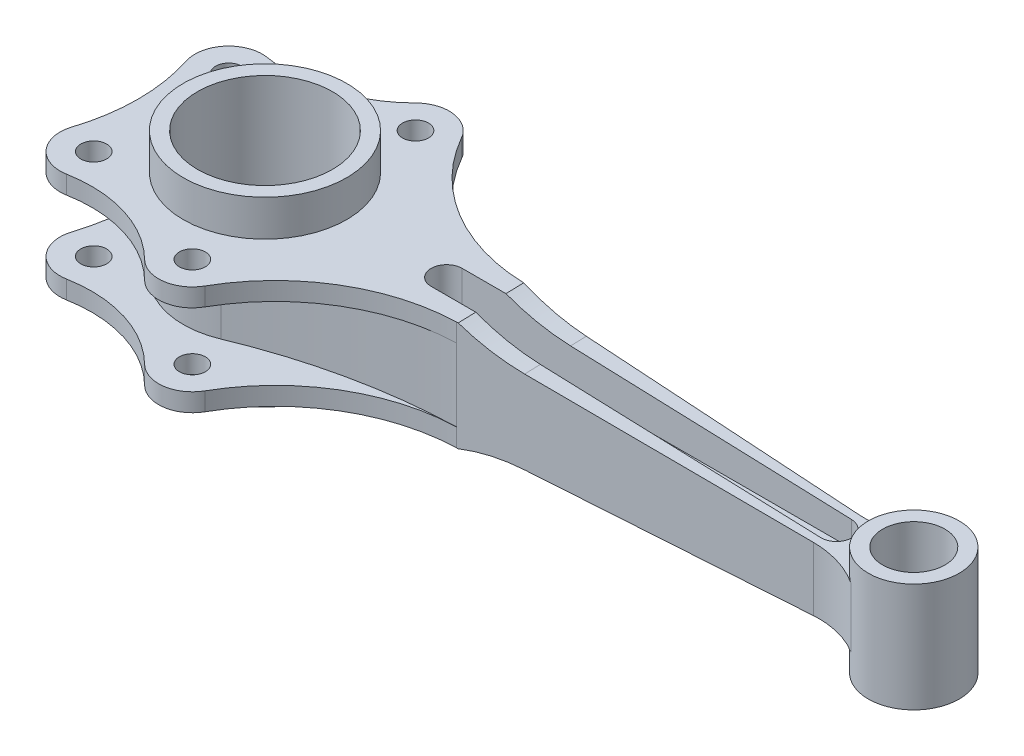
SolidWorks part; units mm, degrees
ref_plane "Front Plane" through (0, 0, 0) normal (0, 0, 1) x (1, 0, 0)
ref_plane "Top Plane" through (0, 0, 0) normal (0, 1, 0) x (1, 0, 0)
ref_plane "Right Plane" through (0, 0, 0) normal (1, 0, 0) x (0, 0, -1)
sketch "Sketch1" plane through (0, 0, 0) normal (0, 1, 0) x (1, 0, 0)
  line L0 (-214.1842, 32.158) -> (132.5363, 32.158) construction
  line L1 (85.3242, 41.158) -> (-48.2027, 45.158)
  line L2 (85.3242, 23.158) -> (-48.2027, 19.158)
  circle A0 centre (-134.9637, 32.158) radius 26
  circle A1 centre (-134.9637, 32.158) radius 31.5
  circle A2 centre (115.0363, 32.158) radius 12
  circle A3 centre (115.0363, 32.158) radius 17.5
  arc A4 (-187.3406, 54.1815) -> (-187.3406, 10.1345) centre (-255.8896, 32.158) cw
  arc A5 (-187.3406, 54.1815) -> (-172.6249, 70.9459) centre (-174.9637, 58.158) cw
  arc A6 (-172.6249, 70.9459) -> (-129.1104, 84.3959) centre (-163.7642, 119.395) ccw
  arc A7 (-129.1104, 84.3959) -> (-108.6587, 81.5766) centre (-119.9637, 75.158) cw
  arc A8 (-108.6587, 81.5766) -> (-48.2027, 45.158) centre (-46.0468, 117.1257) ccw
  arc A9 (105.4816, 46.8194) -> (85.3242, 41.158) centre (86.3722, 76.1423) cw
  arc A10 (105.4816, 17.4966) -> (85.3242, 23.158) centre (86.3722, -11.8263) ccw
  arc A11 (-108.6587, -17.2606) -> (-48.2027, 19.158) centre (-46.0468, -52.8097) cw
  arc A12 (-129.1104, -20.0798) -> (-108.6587, -17.2606) centre (-119.9637, -10.842) ccw
  arc A13 (-172.6249, -6.6299) -> (-129.1104, -20.0798) centre (-163.7642, -55.079) cw
  arc A14 (-187.3406, 10.1345) -> (-172.6249, -6.6299) centre (-174.9637, 6.158) ccw
  arc A15 (-48.2027, 45.158) -> (-122.8601, 61.2398) centre (-41.8931, 255.783) cw
  arc A16 (-48.2027, 19.158) -> (-122.8601, 3.0762) centre (-41.8931, -191.467) ccw
  dimension "D1" = 63
  dimension "D2" = 52
  dimension "D3" = 24
  dimension "D4" = 35
  dimension "D5" = 13
  dimension "D6" = 13
  dimension "D7" = 72
  dimension "D9" = 72
  dimension "D12" = 17
  dimension "D13" = 35
  dimension "D8" = 26
  dimension "D10" = 40
  dimension "D11" = 15
  dimension "D14" = 9
  dimension "D15" = 250
  dimension "D16" = 13
extrude "Boss-Extrude1" add sketch "Sketch1" along normal blind 35 contours L0 A1 A0 | A1 L0 A0 region at (-134.9637, 0, -58.8624) region at (-106.2137, 0, -31.4536)
extrude "Boss-Extrude3" add sketch "Sketch1<5>" along normal blind 7 from offset 14 contours L0 A14 A13 A12 A11 A1 | L0 A1 A8 A7 A6 A5 region at (-85.8889, 0, -51.5393)
sketch "Sketch1<5>" plane through (0, 0, 0) normal (0, 1, 0) x (1, 0, 0) same geometry as "Sketch1"
extrude "Boss-Extrude4" add sketch "Sketch1<7>" along normal up to surface (21 mm away) contours L0 L2 A10 A3 | L0 A3 A9 L1 region at (-17.7787, 0, -32.158) up to face at (-132.7972, 21, -32.158)
sketch "Sketch1<7>" plane through (0, 0, 0) normal (0, 1, 0) x (1, 0, 0) same geometry as "Sketch1"
sketch "Sketch2" plane through (-0.6166, 0, -20.5835) normal (0.0299, 0, 0.9996) x (0.9996, 0, -0.0299)
  line L2 (-46.9403, 2.5) -> (106.8362, 2.5)
  line L3 (106.8362, 21) -> (106.8362, 0) construction
  line L5 (106.8362, 11.5) -> (-22.0625, 16.0012)
  line L6 (-107.9403, 35) -> (-159.9403, 35) construction
  line L7 (-107.9403, 35) -> (-159.9403, 35)
  line L8 (85.9794, 21) -> (-47.6074, 21) construction
  line L9 (106.8362, 11.5) -> (106.8362, 2.5)
  line L10 (85.9794, 0) -> (-47.6074, 0) construction
  line L11 (-46.9403, 21) -> (-46.9403, 2.5)
  line L12 (-46.9403, 23.4049) -> (106.8362, 23.4049)
  line L13 (106.8362, 19.8993) -> (106.8362, 11.5)
  line L14 (106.8362, 23.4049) -> (106.8362, 19.8993)
  line L15 (-46.9403, 23.4049) -> (-46.9403, 21)
  arc A1 (-46.9403, 21) -> (-22.0625, 16.0012) centre (-19.3404, 93.9537) ccw
  point P13 (-133.9403, 35)
  line M1 (85.9794, 0) -> (85.9794, 21)
  line M2 (85.9794, 21) -> (-47.6074, 21)
  dimension "D1" = 87
  dimension "D2" = 78
  dimension "D3" = 2.5
  dimension "D4" = 2
  dimension "D5" = 9
extrude "Cut-Extrude1" cut sketch "Sketch2" against normal through all both and the other way through all contours L12 L15 L5 L13 L14 M2 M1 | A1 L5 M2 M1 region at (29.6584, 17.6251, -21.4905) region at (-45.9941, 22.2024, -19.2242)
extrude "Boss-Extrude5" add sketch "Sketch1<8>" along normal blind 21 contours A3 L0 A2 | L0 A3 A2 region at (99.9944, 0, -40.3095) region at (100.2863, 0, -31.7667)
sketch "Sketch1<8>" plane through (0, 0, 0) normal (0, 1, 0) x (1, 0, 0) same geometry as "Sketch1"
mirror "Mirror1" about plane through (0, 0, 0) normal (0, 1, 0) of bodies 106
sketch "Sketch3" plane through (0, 21, 0) normal (0, 1, 0) x (1, 0, 0)
  line L0 (85.0363, 32.158) -> (-64.9637, 32.158) construction
  line L1 (85.0363, 26.158) -> (-64.9637, 26.158)
  line L2 (85.0363, 38.158) -> (-64.9637, 38.158)
  arc A0 (85.0363, 26.158) -> (85.0363, 38.158) centre (85.0363, 32.158) ccw
  arc A1 (-64.9637, 38.158) -> (-64.9637, 26.158) centre (-64.9637, 32.158) ccw
  circle A3 centre (115.0363, 32.158) radius 17.5
  circle A4 centre (115.0363, 32.158) radius 17.5
  point P3 (10.0363, 32.158)
  line M3 (-47.5358, 19.178) -> (-48.3142, 45.1614)
  dimension "D4" = 6
  dimension "D2" = 30
  dimension "D3" = 150
  dimension "D1" = 0
extrude "Cut-Extrude2" cut sketch "Sketch3" against normal blind 18.5 contours L1 A0 L2 M3 | L2 A1 L1 A0 region at (20.9185, 21, -32.1606)
mirror "Mirror2" about plane through (0, 0, 0) normal (0, 1, 0) of "Cut-Extrude2"
sketch "Sketch4" plane through (0, 21, 0) normal (0, 1, 0) x (1, 0, 0)
  line L5 (-64.9637, 38.158) -> (-48.1044, 38.158)
  line L6 (-48.1044, 38.158) -> (-48.3142, 45.1614)
  line L7 (-48.2027, 19.158) -> (-47.5358, 19.178)
  line L8 (-47.5358, 19.178) -> (-47.7449, 26.158)
  line L9 (-47.7449, 26.158) -> (-64.9637, 26.158)
  line L10 (-64.9637, 38.158) -> (-48.1044, 38.158)
  line L11 (-48.1044, 38.158) -> (-48.3142, 45.1614)
  line L12 (-48.2027, 19.158) -> (-47.5358, 19.178)
  line L13 (-47.5358, 19.178) -> (-47.7449, 26.158)
  line L14 (-47.7449, 26.158) -> (-64.9637, 26.158)
  circle A0 centre (-174.9637, 58.158) radius 5
  circle A1 centre (-119.9637, 75.158) radius 5
  circle A2 centre (-119.9637, -10.842) radius 5
  circle A3 centre (-174.9637, 6.158) radius 5
  arc A10 (-108.6587, 81.5766) -> (-48.3142, 45.1614) centre (-46.0468, 117.1257) ccw
  arc A11 (-108.6587, 81.5766) -> (-129.1104, 84.3959) centre (-119.9637, 75.158) ccw
  arc A12 (-172.6249, 70.9459) -> (-129.1104, 84.3959) centre (-163.7642, 119.395) ccw
  arc A13 (-172.6249, 70.9459) -> (-187.3406, 54.1815) centre (-174.9637, 58.158) ccw
  arc A14 (-187.3406, 10.1345) -> (-187.3406, 54.1815) centre (-255.8896, 32.158) ccw
  arc A15 (-187.3406, 10.1345) -> (-172.6249, -6.6299) centre (-174.9637, 6.158) ccw
  arc A16 (-129.1104, -20.0798) -> (-172.6249, -6.6299) centre (-163.7642, -55.079) ccw
  arc A17 (-129.1104, -20.0798) -> (-108.6587, -17.2606) centre (-119.9637, -10.842) ccw
  arc A18 (-48.2027, 19.158) -> (-108.6587, -17.2606) centre (-46.0468, -52.8097) ccw
  arc A19 (-64.9637, 38.158) -> (-64.9637, 26.158) centre (-64.9637, 32.158) ccw
  arc A20 (-108.6587, 81.5766) -> (-48.3142, 45.1614) centre (-46.0468, 117.1257) ccw
  arc A21 (-108.6587, 81.5766) -> (-129.1104, 84.3959) centre (-119.9637, 75.158) ccw
  arc A22 (-172.6249, 70.9459) -> (-129.1104, 84.3959) centre (-163.7642, 119.395) ccw
  arc A23 (-172.6249, 70.9459) -> (-187.3406, 54.1815) centre (-174.9637, 58.158) ccw
  arc A24 (-187.3406, 10.1345) -> (-187.3406, 54.1815) centre (-255.8896, 32.158) ccw
  arc A25 (-187.3406, 10.1345) -> (-172.6249, -6.6299) centre (-174.9637, 6.158) ccw
  arc A26 (-129.1104, -20.0798) -> (-172.6249, -6.6299) centre (-163.7642, -55.079) ccw
  arc A27 (-129.1104, -20.0798) -> (-108.6587, -17.2606) centre (-119.9637, -10.842) ccw
  arc A28 (-48.2027, 19.158) -> (-108.6587, -17.2606) centre (-46.0468, -52.8097) ccw
  arc A29 (-64.9637, 38.158) -> (-64.9637, 26.158) centre (-64.9637, 32.158) ccw
  dimension "D2" = 10
  dimension "D3" = 10
  dimension "D4" = 10
  dimension "D5" = 10
  dimension "D1" = 0
extrude "Cut-Extrude3" cut sketch "Sketch4" against normal through all both and the other way through all contours A0 | A3 | A2 | A1 region at (-174.9637, 21, -58.158)
